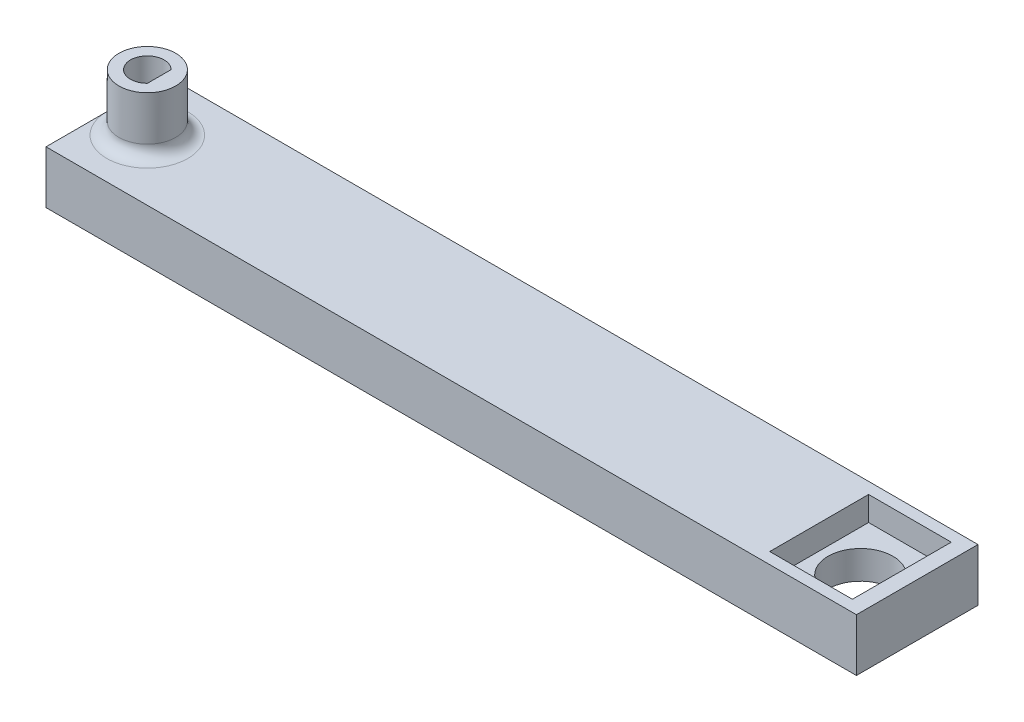
SolidWorks part; units mm, degrees
ref_plane "Front Plane" through (0, 0, 0) normal (0, 0, 1) x (1, 0, 0)
ref_plane "Top Plane" through (0, 0, 0) normal (0, 1, 0) x (1, 0, 0)
ref_plane "Right Plane" through (0, 0, 0) normal (1, 0, 0) x (0, 0, -1)
sketch "Sketch2" plane through (0, 0, 0) normal (0, 1, 0) x (1, 0, 0)
  line L1 (-50, -7.5) -> (50, -7.5)
  line L2 (-50, -7.5) -> (-50, 7.5)
  line L3 (-50, 7.5) -> (50, 7.5)
  line L4 (50, -7.5) -> (50, 7.5)
  line L5 (-50, -7.5) -> (50, 7.5) construction
  line L6 (-50, 7.5) -> (50, -7.5) construction
  point P0 (0, 0)
  dimension "D1" = 100
  dimension "D2" = 15
extrude "Boss-Extrude1" add sketch "Sketch2" along normal mid plane 6.5
other "Cavity1" [suppressed]
other "1Prong<1>@RobotAssem1"
sketch "Sketch4" plane through (0, 3.25, 0) normal (0, 1, 0) x (1, 0, 0)
  line L0 (-47.5, 3.5) -> (-47.5, -3.5)
  line L1 (-50, 7.5) -> (-50, -7.5)
  line L2 (-50, 7.5) -> (-50, -7.5)
  line L6 (50, -7.5) -> (50, 7.5)
  line L7 (50, -7.5) -> (50, 7.5)
  line L8 (50, 7.5) -> (-50, 7.5)
  line L9 (50, 7.5) -> (-50, 7.5)
  line L10 (-50, -7.5) -> (50, -7.5)
  line L11 (-50, -7.5) -> (50, -7.5)
  dimension "D1" = 0
extrude "Cut-Extrude1" [suppressed] cut sketch "Sketch4" against normal up to surface (5.75 mm away)
sketch "Sketch17" [suppressed] plane through (0, 3.25, 0) normal (0, 1, 0) x (1, 0, 0)
  line L0 (-47.5, -6.25) -> (-47.5, 6.25) construction
  line L1 (-47.5, 4.5) -> (-47.5, 3.5)
  line L2 (-47.5, -3.5) -> (-47.5, -4.5)
  arc A0 (-47.5, -3.5) -> (-47.5, 3.5) centre (-47.5, 0) ccw
  arc A1 (-47.5, -4.5) -> (-47.5, 4.5) centre (-47.5, 0) ccw
  dimension "D1" = 1
extrude "Cut-Extrude9" [suppressed] cut sketch "Sketch17" against normal up to surface (5.75 mm away)
sketch "Sketch15" plane through (0, 0, 0) normal (0, 0, 1) x (1, 0, 0)
  line L0 (50, -3.25) -> (-50, -3.25) construction
  line L1 (23.5, -3.25) -> (15, -3.25)
  line L2 (23.5, -3.25) -> (23.5, 1)
  line L3 (23.5, 1) -> (15, 1)
  line L4 (15, -3.25) -> (15, 1)
  line L6 (15, 1) -> (10, 1)
  line L8 (15, -2.25) -> (10, -2.25)
  line L9 (10, 1) -> (10, -2.25)
  line L10 (50, 3.25) -> (50, -3.25) construction
  dimension "D1" = 35
  dimension "D2" = 8.5
  dimension "D3" = 5
  dimension "D4" = 3.25
  dimension "D5" = 1
extrude "Cut-Extrude8" cut sketch "Sketch15" against normal mid plane 2.25 contours L4 L1 L2 L3 | L6 L9 L8 L4
sketch "Sketch18" plane through (0, 3.25, 0) normal (0, 1, 0) x (1, 0, 0)
  line L0 (-55, 0) -> (55, 0) construction
  line L1 (37.9, -6.1) -> (48.1, -6.1)
  line L2 (37.9, -6.1) -> (37.9, 6.1)
  line L3 (37.9, 6.1) -> (48.1, 6.1)
  line L4 (48.1, -6.1) -> (48.1, 6.1)
  line L5 (37.9, -6.1) -> (48.1, 6.1) construction
  line L6 (37.9, 6.1) -> (48.1, -6.1) construction
  line L8 (50, -7.5) -> (50, 7.5) construction
  point P0 (43, 0)
  dimension "D1" = 10.2
  dimension "D2" = 7
  dimension "D3" = 12.2
extrude "Cut-Extrude10" cut sketch "Sketch18" against normal blind 3
sketch "Sketch19" plane through (0, -3.25, 0) normal (0, -1, 0) x (1, 0, 0)
  line L0 (3.575, 0) -> (-3.575, 0) construction
  line L1 (50, 7.5) -> (50, -7.5) construction
  circle A0 centre (43, 0) radius 4
  dimension "D1" = 8
  dimension "D2" = 7
extrude "Cut-Extrude11" cut sketch "Sketch19" against normal through all both and the other way through all
sketch "Sketch20" plane through (0, 3.25, 0) normal (0, 1, 0) x (1, 0, 0)
  line L0 (-3.575, 0) -> (3.575, 0) construction
  line L1 (-50, 7.5) -> (-50, -7.5) construction
  circle A0 centre (-45, 0) radius 3.5
  dimension "D1" = 7
  dimension "D2" = 5
extrude "Boss-Extrude2" add sketch "Sketch20" along normal blind 7
sketch "Sketch21" plane through (0, 10.25, 0) normal (0, 1, 0) x (1, 0, 0)
  line L0 (-43.525, 1.4595) -> (-43.525, -1.4595)
  circle A0 centre (-45, 0) radius 2.075
  point P3 (-47.075, 0)
  dimension "D1" = 4.15
  dimension "D2" = 3.55
extrude "Cut-Extrude12" cut sketch "Sketch21" against normal blind 9.5 contours L0 A0
fillet "Fillet1" radius 1.5 1 edges at (-45, 3.25, -3.5)
